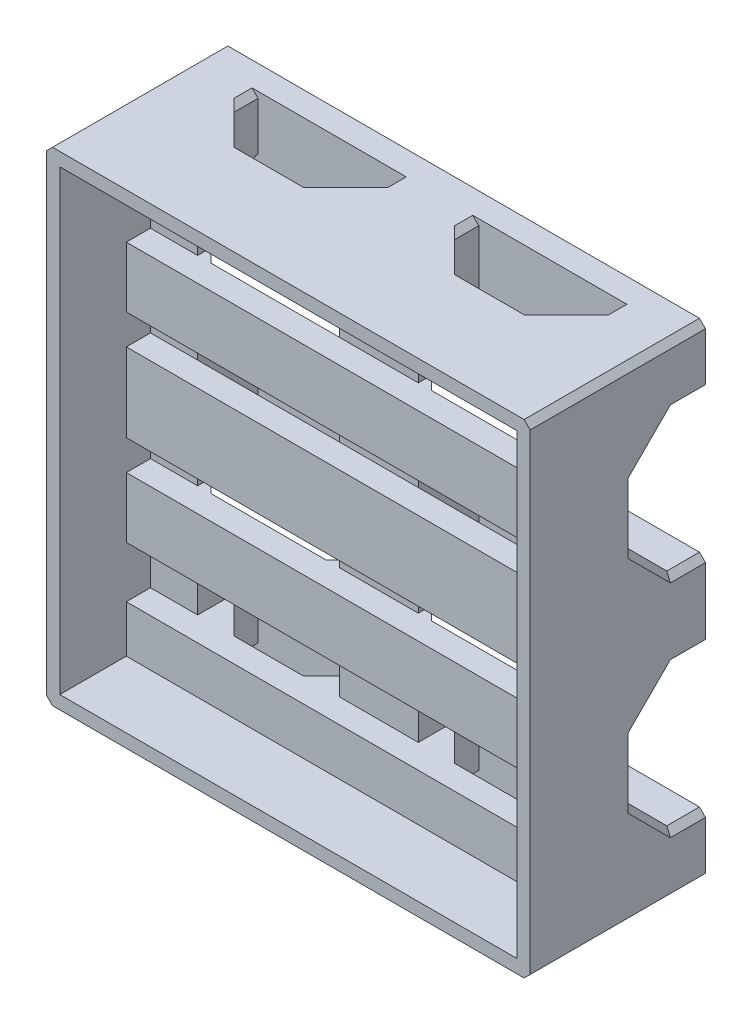
SolidWorks part; units mm, degrees
ref_plane "Alzado" through (0, 0, 0) normal (1, 0, 0) x (0, 1, 0)
ref_plane "Planta" through (0, 0, 0) normal (0, 0, 1) x (0, 1, 0)
ref_plane "Vista lateral" through (0, 0, 0) normal (0, 1, 0) x (-1, 0, 0)
sketch "Croquis1" plane through (0, 0, 0) normal (0, 0, 1) x (0, 1, 0)
  line L0 (0, 0) -> (40, 0) construction
  line L5 (0, 0) -> (0, 40) construction
  line L7 (-30, 40) -> (-40, -40) construction
  line L8 (-6.5, 40) -> (6.5, 40)
  line L9 (-6.5, 40) -> (-6.5, -40)
  line L10 (-6.5, -40) -> (6.5, -40)
  line L11 (6.5, 40) -> (6.5, -40)
  line L12 (-6.5, 40) -> (6.5, -40) construction
  line L13 (-6.5, -40) -> (6.5, 40) construction
  line L14 (30, -40) -> (40, -40)
  line L15 (30, -40) -> (30, 40)
  line L16 (30, 40) -> (40, 40)
  line L17 (40, -40) -> (40, 40)
  line L18 (30, -40) -> (40, 40) construction
  line L19 (30, 40) -> (40, -40) construction
  line L20 (-30, -40) -> (-40, 40) construction
  line L21 (-40, -40) -> (-40, 40)
  line L22 (-30, 40) -> (-40, 40)
  line L23 (-30, -40) -> (-30, 40)
  line L24 (-30, -40) -> (-40, -40)
  point P9 (35, 0)
  point P18 (-35, 0)
  dimension "D1" = 40
  dimension "D2" = 40
  dimension "D3" = 13
  dimension "D4" = 10
extrude "Saliente-Extruir1" add sketch "Croquis1" along normal blind 4
sketch "Croquis2" plane through (0, 0, 4) normal (0, 0, 1) x (1, 0, 0)
  line L0 (40, 0) -> (0, 0) construction
  line L1 (40, 30) -> (40, 40) construction
  line L2 (40, -6.5) -> (40, 6.5) construction
  line L3 (0, 0) -> (0, 35) construction
  line L5 (-40, -6.5) -> (40, -6.5) construction
  line L6 (-6.5, 6.5) -> (6.5, 6.5)
  line L7 (-6.5, 6.5) -> (-6.5, -6.5)
  line L8 (-6.5, -6.5) -> (6.5, -6.5)
  line L9 (6.5, 6.5) -> (6.5, -6.5)
  line L10 (-6.5, 6.5) -> (6.5, -6.5) construction
  line L11 (-6.5, -6.5) -> (6.5, 6.5) construction
  line L12 (-40, 6.5) -> (-40, -6.5) construction
  line L13 (-30, -6.5) -> (-40, -6.5)
  line L14 (-30, -6.5) -> (-30, 6.5)
  line L15 (-30, 6.5) -> (-40, 6.5)
  line L16 (-40, -6.5) -> (-40, 6.5)
  line L17 (-30, -6.5) -> (-40, 6.5) construction
  line L18 (-30, 6.5) -> (-40, -6.5) construction
  line L19 (30, 6.5) -> (40, -6.5) construction
  line L20 (30, -6.5) -> (40, 6.5) construction
  line L21 (40, -6.5) -> (40, 6.5)
  line L22 (30, 6.5) -> (40, 6.5)
  line L23 (30, -6.5) -> (30, 6.5)
  line L24 (30, -6.5) -> (40, -6.5)
  line L25 (-40, 30) -> (40, 30) construction
  line L26 (-6.5, 40) -> (6.5, 40)
  line L27 (-6.5, 40) -> (-6.5, 30)
  line L28 (-6.5, 30) -> (6.5, 30)
  line L29 (6.5, 40) -> (6.5, 30)
  line L30 (-6.5, 40) -> (6.5, 30) construction
  line L31 (-6.5, 30) -> (6.5, 40) construction
  line L32 (40, 30) -> (30, 40) construction
  line L33 (-40, 40) -> (-30, 40)
  line L34 (-40, 40) -> (-40, 30)
  line L35 (-40, 30) -> (-30, 30)
  line L36 (-30, 40) -> (-30, 30)
  line L37 (-40, 40) -> (-30, 30) construction
  line L38 (-40, 30) -> (-30, 40) construction
  line L39 (40, 40) -> (30, 30) construction
  line L40 (30, 40) -> (30, 30)
  line L41 (40, 30) -> (30, 30)
  line L42 (40, 40) -> (40, 30)
  line L43 (40, 40) -> (30, 40)
  line L44 (40, -40) -> (30, -30) construction
  line L45 (-40, -30) -> (-30, -40) construction
  line L46 (-40, -40) -> (-30, -30) construction
  line L47 (40, -30) -> (30, -40) construction
  line L48 (-6.5, -30) -> (6.5, -40) construction
  line L49 (-6.5, -40) -> (6.5, -30) construction
  line L50 (40, -40) -> (30, -40)
  line L51 (40, -40) -> (40, -30)
  line L52 (40, -30) -> (30, -30)
  line L53 (30, -40) -> (30, -30)
  line L54 (-30, -40) -> (-30, -30)
  line L55 (-40, -30) -> (-30, -30)
  line L56 (-40, -40) -> (-40, -30)
  line L57 (-40, -40) -> (-30, -40)
  line L58 (6.5, -40) -> (6.5, -30)
  line L59 (-6.5, -30) -> (6.5, -30)
  line L60 (-6.5, -40) -> (-6.5, -30)
  line L61 (-6.5, -40) -> (6.5, -40)
  point P8 (40, 35)
  point P14 (-35, 0)
  point P25 (35, 0)
  point P33 (-35, 35)
  point P43 (35, 35)
  point P56 (35, -35)
  point P57 (-35, -35)
  point P58 (40, -35)
  dimension "D1" = 13
  dimension "D2" = 10
extrude "Saliente-Extruir2" add sketch "Croquis2" along normal blind 10
sketch "Croquis3" plane through (0, 0, 14) normal (0, 0, 1) x (1, 0, 0)
  line L0 (0, 0) -> (40, 0) construction
  line L1 (40, -6.5) -> (40, 6.5) construction
  line L2 (0, 0) -> (0, 40) construction
  line L3 (6.5, 40) -> (-6.5, 40) construction
  line L4 (-40, 6.5) -> (-40, -6.5) construction
  line L5 (-6.5, -40) -> (6.5, -40)
  line L6 (-6.5, -40) -> (-6.5, 40)
  line L7 (-6.5, 40) -> (6.5, 40)
  line L8 (6.5, -40) -> (6.5, 40)
  line L9 (-6.5, -40) -> (6.5, 40) construction
  line L10 (-6.5, 40) -> (6.5, -40) construction
  line L11 (-40, -40) -> (-30, -40)
  line L12 (-40, -40) -> (-40, 40)
  line L13 (-40, 40) -> (-30, 40)
  line L14 (-30, -40) -> (-30, 40)
  line L15 (-40, -40) -> (-30, 40) construction
  line L16 (-40, 40) -> (-30, -40) construction
  line L17 (-40, -40) -> (-30, -40) construction
  line L18 (40, 40) -> (30, -40) construction
  line L19 (40, -40) -> (30, 40) construction
  line L20 (30, -40) -> (30, 40)
  line L21 (40, 40) -> (30, 40)
  line L22 (40, -40) -> (40, 40)
  line L23 (40, -40) -> (30, -40)
  point P13 (-35, 0)
  point P27 (35, 0)
extrude "Saliente-Extruir3" add sketch "Croquis3" against normal blind 2.2
sketch "Croquis4" plane through (0, 0, 14) normal (0, 0, 1) x (1, 0, 0)
  line L0 (-40, -30) -> (40, -30) construction
  line L1 (40, -30) -> (40, -40) construction
  line L2 (40, -40) -> (-40, -40) construction
  line L3 (-40, -40) -> (-40, -30) construction
  line L4 (-40, 6.5) -> (40, 6.5) construction
  line L5 (40, 6.5) -> (40, -6.5) construction
  line L6 (40, -6.5) -> (-40, -6.5) construction
  line L7 (-40, -6.5) -> (-40, 6.5) construction
  line L8 (-40, 40) -> (40, 40) construction
  line L9 (40, 40) -> (40, 30) construction
  line L10 (40, 30) -> (-40, 30) construction
  line L11 (-40, 30) -> (-40, 40) construction
  line L12 (-40, -30) -> (40, -30)
  line L13 (40, -30) -> (40, -40)
  line L14 (40, -40) -> (-40, -40)
  line L15 (-40, -40) -> (-40, -30)
  line L16 (-40, 6.5) -> (40, 6.5)
  line L17 (40, 6.5) -> (40, -6.5)
  line L18 (40, -6.5) -> (-40, -6.5)
  line L19 (-40, -6.5) -> (-40, 6.5)
  line L20 (-40, 40) -> (40, 40)
  line L21 (40, 40) -> (40, 30)
  line L22 (40, 30) -> (-40, 30)
  line L23 (-40, 30) -> (-40, 40)
  line L24 (0, 0) -> (40, 0) construction
  line L25 (40, -40) -> (40, 40) construction
  line L26 (-40, 21.5) -> (40, 21.5)
  line L27 (-40, 21.5) -> (-40, 11.5)
  line L28 (-40, 11.5) -> (40, 11.5)
  line L29 (40, 21.5) -> (40, 11.5)
  line L30 (-40, 21.5) -> (40, 11.5) construction
  line L31 (-40, 11.5) -> (40, 21.5) construction
  line L32 (-40, -11.5) -> (40, -21.5) construction
  line L33 (-40, -21.5) -> (40, -11.5) construction
  line L34 (40, -21.5) -> (40, -11.5)
  line L35 (-40, -11.5) -> (40, -11.5)
  line L36 (-40, -21.5) -> (-40, -11.5)
  line L37 (-40, -21.5) -> (40, -21.5)
  point P15 (0, 16.5)
  point P27 (0, -16.5)
  dimension "D1" = 5
  dimension "D2" = 10
extrude "Saliente-Extruir4" add sketch "Croquis4" along normal blind 4
sketch "Croquis5" plane through (0, 0, 14) normal (0, 0, 1) x (1, 0, 0)
  line L0 (-37.8, -37.8) -> (-37.8, 37.8)
  line L1 (40, -40) -> (-40, -40)
  line L2 (40, -40) -> (40, 40)
  line L3 (40, 40) -> (-40, 40)
  line L4 (-40, -40) -> (-40, 40)
  line L5 (40, -40) -> (-40, 40) construction
  line L6 (40, 40) -> (-40, -40) construction
  line L7 (37.8, 37.8) -> (-37.8, 37.8)
  line L8 (37.8, -37.8) -> (37.8, 37.8)
  line L9 (37.8, -37.8) -> (-37.8, -37.8)
  point P0 (0, 0)
  dimension "D1" = 2.2
extrude "Saliente-Extruir5" add sketch "Croquis5" along normal blind 15
chamfer "Chaflán2" distance 6.4 angle 45 12 edges at (35, -30, 11.8) (0, 6.5, 11.8) (0, -6.5, 11.8) (-35, -6.5, 11.8) (-35, 30, 11.8) (0, 30, 11.8) (-35, 6.5, 11.8) (-35, -30, 11.8) (0, -30, 11.8) (35, 6.5, 11.8) (35, 30, 11.8) (35, -6.5, 11.8)
chamfer "Chaflán3" distance 6 angle 45 8 edges at (30, -35, 14) (6.5, -35, 14) (-6.5, -35, 14) (-30, -35, 14) (-6.5, 35, 14) (-30, 35, 14) (6.5, 35, 14) (30, 35, 14)
chamfer "Chaflán4" distance 2.2 angle 45 7 edges at (6.5, -16.5, 14) (6.5, 16.5, 14) (30, -16.5, 14) (30, 16.5, 14) (-6.5, -16.5, 14) (-30, -16.5, 14) (-30, 16.5, 14)
sketch "Croquis6" plane through (-40, 0, 0) normal (-1, 0, 0) x (0, -1, 0)
  line L0 (0, 0) -> (0, 29) construction
  line L1 (-40, 29) -> (40, 29) construction
  line L2 (0, 14.5) -> (32.8519, 14.5) construction
  line L3 (-5, 9.5) -> (5, 9.5)
  line L8 (5, 9.5) -> (3, 19.5)
  line L9 (3, 19.5) -> (-3, 19.5)
  line L10 (-5, 9.5) -> (-3, 19.5)
  point P12 (0, 19.5)
  point P13 (0, 9.5)
  dimension "D1" = 10
  dimension "D2" = 5
  dimension "D3" = 3
extrude "Cortar-Extruir1" cut sketch "Croquis6" against normal blind 0.4
fillet "Redondeo1" radius 1 4 edges at (-39.8, -3, 19.5) (-39.8, 3, 19.5) (-39.8, -5, 9.5) (-39.8, 5, 9.5)
chamfer "Chaflán1" distance 1 angle 45 44 edges at (40, -30, 2.7) (-30, 30, 4.7) (-30, -6.5, 4.7) (-30, 6.5, 4.7) (6.5, -6.5, 4.7) (6.5, 6.5, 4.7) (-6.5, 6.5, 4.7) (-6.5, 30, 4.7) (-30, 40, 6) (30, 6.5, 4.7) (30, 30, 4.7) (-6.5, 40, 6) (6.5, 40, 6) (30, 40, 6) (-40, 40, 14.5) (-40, 30, 2.7) (-40, 6.5, 2.7) (-40, -6.5, 2.7) (-40, -30, 2.7) (-40, -40, 14.5) (30, -30, 4.7) (30, -40, 6) (-6.5, -40, 6) (-30, -30, 4.7) (-30, -40, 6) (6.5, -30, 4.7) (6.5, -40, 6) (40, 40, 14.5) (40, 30, 2.7) (40, 6.5, 2.7) (40, -6.5, 2.7) (40, -40, 14.5) (40, -26.8, 8.6) (-40, 26.8, 8.6) (-40, 18.25, 11.8) (-40, 9.7, 8.6) (-40, -9.7, 8.6) (-40, -18.25, 11.8) (-40, -26.8, 8.6) (40, 26.8, 8.6) (40, 18.25, 11.8) (40, 9.7, 8.6) (40, -18.25, 11.8) (40, -9.7, 8.6)
